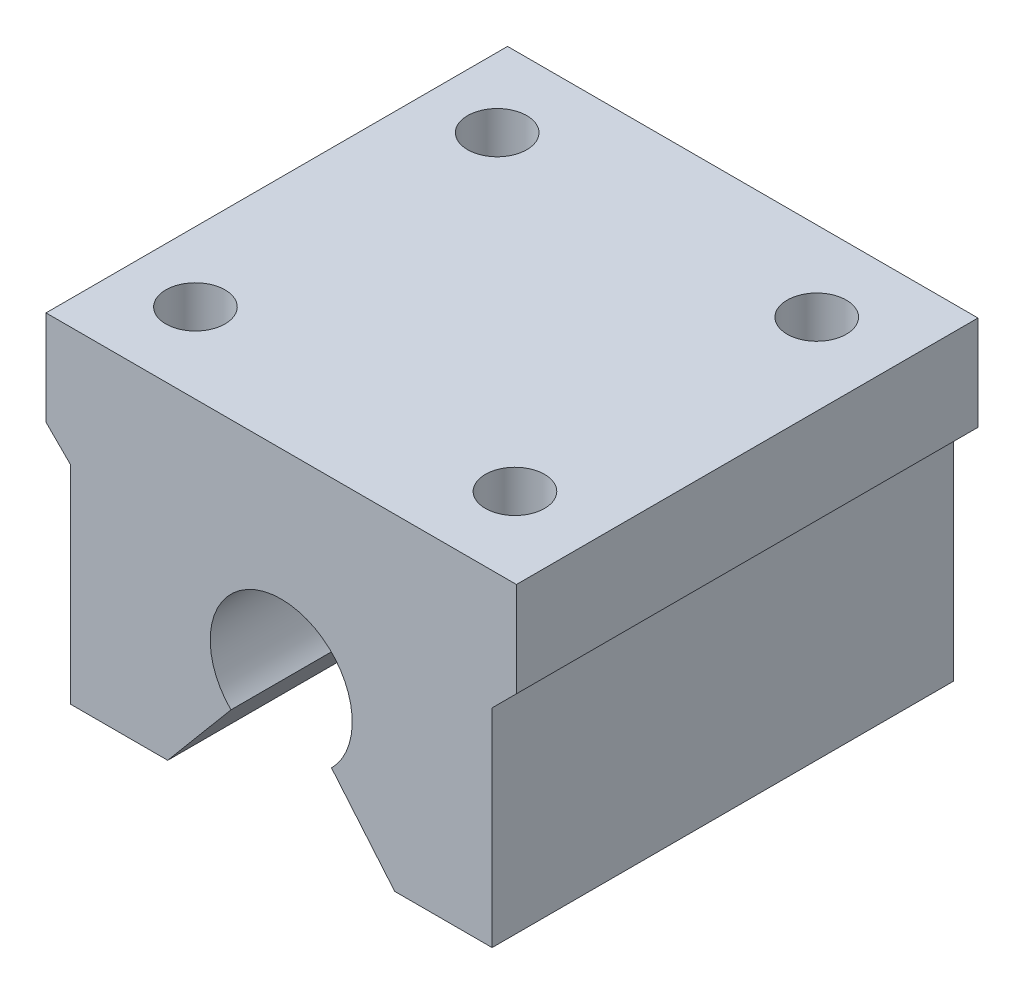
SolidWorks part; units mm, degrees
ref_plane "Front Plane" through (0, 0, 0) normal (0, 0, 1) x (1, 0, 0)
ref_plane "Top Plane" through (0, 0, 0) normal (0, 1, 0) x (1, 0, 0)
ref_plane "Right Plane" through (0, 0, 0) normal (1, 0, 0) x (0, 0, -1)
sketch "Sketch1" plane through (0, 0, 0) normal (0, 0, 1) x (1, 0, 0)
  line L0 (0, 0) -> (0, 38.5119) construction
  line L1 (-4.25, -4.2353) -> (38.3645, -4.2353) construction
  line L2 (19.875, 17) -> (-19.875, 17)
  line L3 (-19.875, 17) -> (-19.875, 9)
  line L4 (-19.875, 9) -> (-17.8185, 6.9435)
  line L5 (-17.8185, 6.9435) -> (-17.8185, -10.6)
  line L6 (-17.8185, -10.6) -> (-9.5906, -10.6)
  line L7 (-9.5906, -10.6) -> (-4.25, -4.2353)
  line L8 (9.5906, -10.6) -> (4.25, -4.2353)
  line L9 (17.8185, -10.6) -> (9.5906, -10.6)
  line L10 (17.8185, 6.9435) -> (17.8185, -10.6)
  line L11 (19.875, 9) -> (17.8185, 6.9435)
  line L12 (19.875, 17) -> (19.875, 9)
  arc A0 (-4.25, -4.2353) -> (4.25, -4.2353) centre (0, 0) cw
  point P19 (0, 17)
  dimension "D1" = 19.875
  dimension "D3" = 6
  dimension "D2" = 4.25
  dimension "D4" = 8
  dimension "D5" = 27.6
  dimension "D6" = 80
  dimension "D7" = 17
extrude "Boss-Extrude1" add sketch "Sketch1" along normal blind 39
sketch "Sketch2" plane through (0, 17, 0) normal (0, 1, 0) x (1, 0, 0)
  line L1 (-0.5, 2.3584) -> (-0.5, -4.8766) construction
  line L2 (-20, -19.5) -> (-15.4499, -19.5) construction
  circle A0 centre (-14, -32.25) radius 2.5
  circle A1 centre (13, -32.25) radius 2.5
  circle A2 centre (-14, -6.75) radius 2.5
  circle A3 centre (13, -6.75) radius 2.5
  dimension "D1" = 13.5
  dimension "D2" = 13.5
  dimension "D4" = 13.5
  dimension "D5" = 12.75
  dimension "D6" = 12.75
  dimension "D7" = 12.75
  dimension "D8" = 5
  dimension "D9" = 5
  dimension "D10" = 5
  dimension "D11" = 5
  dimension "D3" = 13.5
extrude "Cut-Extrude1" cut sketch "Sketch2" against normal blind 10
